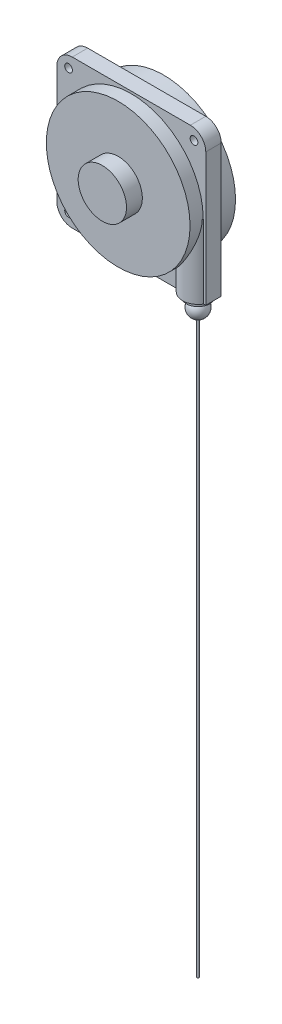
SolidWorks part; units mm, degrees
material "Żeliwo ciągliwe"
ref_plane "Płaszczyzna przednia" through (0, 0, 0) normal (0, 0, 1) x (1, 0, 0)
ref_plane "Płaszczyzna górna" through (0, 0, 0) normal (0, 1, 0) x (1, 0, 0)
ref_plane "Płaszczyzna prawa" through (0, 0, 0) normal (1, 0, 0) x (0, 0, -1)
sketch "Szkic1" plane through (0, 0, 0) normal (0, 0, 1) x (1, 0, 0)
  line L1 (-96.5, 96) -> (96.5, 96)
  line L2 (-96.5, 96) -> (-96.5, -96)
  line L3 (-96.5, -96) -> (96.5, -96)
  line L4 (96.5, 96) -> (96.5, -96)
  line L5 (-96.5, 96) -> (96.5, -96) construction
  line L6 (-96.5, -96) -> (96.5, 96) construction
  point P0 (0, 0)
  dimension "D1" = 193
  dimension "D2" = 192
extrude "Dodanie-wyciągnięcie1" add sketch "Szkic1" along normal mid plane 95
sketch "Szkic2" plane through (0, 0, 0) normal (0, 1, 0) x (1, 0, 0)
  line L0 (0, 0) -> (0, 50000) construction
  line L4 (-93.1085, -10) -> (-93.1085, -26.9655)
  line L5 (-93.1085, -26.9655) -> (-31.3054, -26.9655)
  line L6 (-31.3054, -26.9655) -> (-31.3054, -47.5)
  line L7 (96.5, -47.5) -> (-96.5, -47.5) construction
  line L8 (-31.3054, -47.5) -> (-96.5, -47.5)
  line L9 (-96.5, -47.5) -> (-149.7848, -47.5)
  line L10 (-149.7848, -47.5) -> (-149.7848, -10)
  line L11 (-149.7848, -10) -> (-93.1085, -10)
  line L12 (-93.1085, 10) -> (-149.7848, 10)
  line L13 (-149.7848, 10) -> (-149.7848, 64.6908)
  line L14 (-93.1085, 10) -> (-93.1085, 31.9588)
  line L15 (-93.1085, 31.9588) -> (-34.3743, 47.5)
  line L16 (96.5, 47.5) -> (-96.5, 47.5) construction
  line L17 (-34.3743, 47.5) -> (-34.3743, 64.6908)
  line L18 (-34.3743, 64.6908) -> (-149.7848, 64.6908)
  line L19 (0, 0) -> (50000, 0) construction
  dimension "D1" = 20
revolve "Wycięcie-obrót1" cut sketch "Szkic2" angle 360 about L0
hole_wizard "Otwór Ø10.0 (10)1" positions "Szkic3" profile "Szkic4" hole size "Ø10.0" standard "ISO" end condition through all
sketch "Szkic3" plane through (0, 0, 10) normal (0, 0, 1) x (1, 0, 0)
  line L0 (0, 0) -> (0, 50000) construction
  line L1 (0, 0) -> (50000, 0) construction
  point P0 (-81.25, 81.25)
  point P11 (81.25, 81.25)
  point P13 (-81.25, -81.25)
  dimension "D1" = 162.5
  dimension "D2" = 162.5
sketch "Szkic4" plane through (-81.25, 81.25, 10) normal (1, 0, 0) x (0, -1, 0)
  line L0 (0, 0) -> (0, 57.5)
  line L1 (0, 57.5) -> (5, 57.5)
  line L2 (5, 57.5) -> (5, 0)
  line L5 (5, 0) -> (0, 0)
  line L11 (0, -6.35) -> (0, 107.95) construction
  dimension "Średnica otworu na wylot" = 10
  dimension "Głębokość otworu na wylot" = 57.5
sketch "Szkic5" plane through (0, -96, 0) normal (0, -1, 0) x (1, 0, 0)
  line L0 (96.5, 10) -> (96.5, -10) construction
  circle A0 centre (76.5, 0) radius 20
  dimension "D1" = 40
extrude "Dodanie-wyciągnięcie2" add sketch "Szkic5" against normal blind 95
fillet "Zaokrąglenie1" radius 20 3 edges at (-96.5, -96, 0) (-96.5, 96, 0) (96.5, 96, 0)
ref_axis "Oś1" through (76.5, -1, 0) along (0, -1, 0)
sketch "Szkic6" plane through (0, 0, 0) normal (0, 0, 1) x (1, 0, 0)
  line L0 (76.5, -96) -> (91.5, -96)
  line L1 (76.5, -1) -> (76.5, -140.4695) construction
  line L2 (59.1795, -96) -> (93.8205, -96) construction
  line L3 (91.5, -96) -> (91.5, -102)
  line L4 (91.5, -102) -> (81.2958, -102)
  line L5 (76.5, -95.8289) -> (76.5, -50095.8289) construction
  line L6 (76.5, -96) -> (76.5, -101)
  line L7 (78, -124.9059) -> (78, -864.814)
  line L8 (78, -864.814) -> (76.5, -864.814)
  line L9 (76.5, -864.814) -> (76.5, -96)
  arc A1 (78, -124.9059) -> (81.2958, -102) centre (76.5, -113) ccw
  dimension "D3" = 24
  dimension "D4" = 17
  dimension "D1" = 30
  dimension "D2" = 6
  dimension "D5" = 1.5
revolve "Obrót1" add sketch "Szkic6" angle 360 about L5
